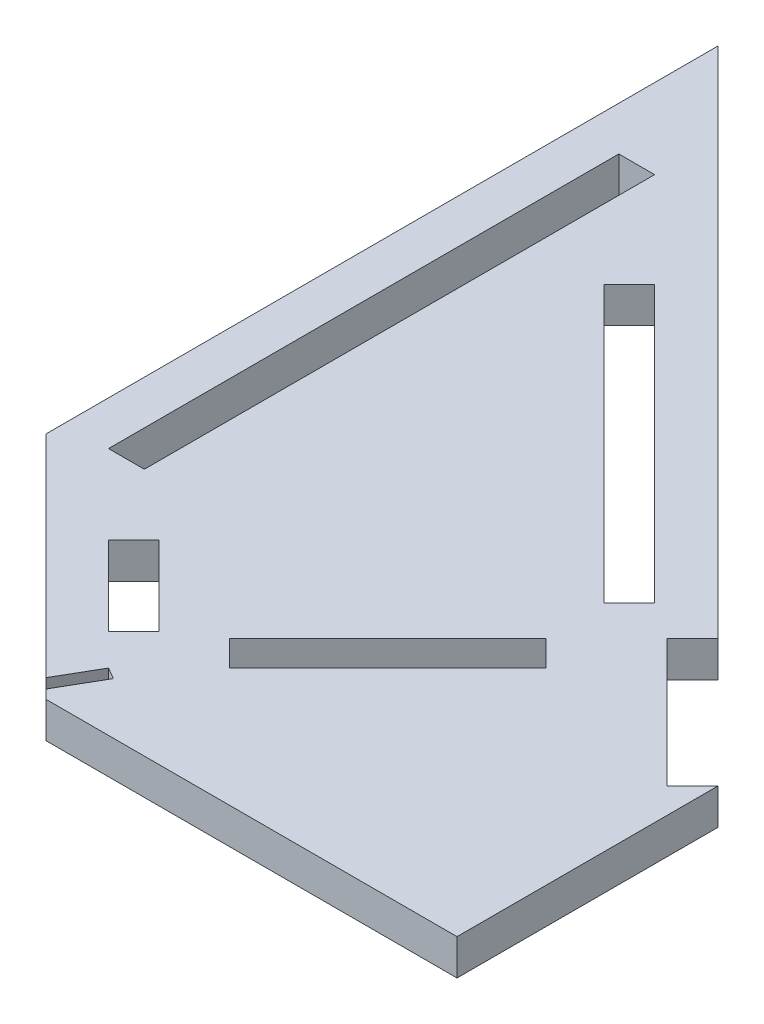
SolidWorks part; units mm, degrees
ref_plane "Front Plane" through (0, 0, 0) normal (0, 0, 1) x (1, 0, 0)
ref_plane "Top Plane" through (0, 0, 0) normal (0, 1, 0) x (1, 0, 0)
ref_plane "Right Plane" through (0, 0, 0) normal (1, 0, 0) x (0, 0, -1)
sketch "Sketch1" plane through (0, 0, 0) normal (0, 1, 0) x (1, 0, 0)
  line L0 (0, 0) -> (0, 58.25)
  line L1 (0, 58.25) -> (-143.0789, 201.3289)
  line L2 (-143.0789, 201.3289) -> (-143.0789, 51.3289)
  line L3 (-143.0789, 51.3289) -> (-95.9462, 4.1962)
  line L4 (-91.75, 0) -> (0, 0)
  line L5 (-93.75, 2) -> (-91.75, 0)
  line L6 (-82.9929, 32.1972) -> (-77.336, 26.5404) construction
  line L7 (-47.6375, 67.5526) -> (-82.9929, 32.1972) construction
  line L8 (-47.6375, 67.5526) -> (-41.9807, 61.8957) construction
  line L17 (-41.9807, 61.8957) -> (-77.336, 26.5404) construction
  line L18 (-109.7154, 142.5174) -> (-48.0839, 80.886)
  line L19 (-48.0839, 80.886) -> (-42.4271, 86.5429)
  line L20 (-42.4271, 86.5429) -> (-104.0585, 148.1743)
  line L21 (-104.0585, 148.1743) -> (-109.7154, 142.5174)
  line L22 (-109.7154, 142.5174) -> (-48.0839, 80.886)
  line L23 (-48.0839, 80.886) -> (-42.4271, 86.5429)
  line L24 (-42.4271, 86.5429) -> (-104.0585, 148.1743)
  line L25 (-104.0585, 148.1743) -> (-109.7154, 142.5174)
  line L34 (-125.2717, 55.4575) -> (-125.2717, 169.3875)
  line L35 (-125.2717, 169.3875) -> (-133.2717, 169.3875)
  line L36 (-133.2717, 169.3875) -> (-133.2717, 55.4575)
  line L37 (-133.2717, 55.4575) -> (-125.2717, 55.4575)
  line L38 (-125.2717, 55.4575) -> (-125.2717, 169.3875)
  line L39 (-125.2717, 169.3875) -> (-133.2717, 169.3875)
  line L40 (-133.2717, 169.3875) -> (-133.2717, 55.4575)
  line L41 (-133.2717, 55.4575) -> (-125.2717, 55.4575)
  line L42 (-82.9929, 32.1972) -> (-77.336, 26.5404)
  line L43 (-47.6375, 67.5526) -> (-82.9929, 32.1972)
  line L44 (-47.6375, 67.5526) -> (-41.9807, 61.8957)
  line L45 (-41.9807, 61.8957) -> (-77.336, 26.5404)
  line L47 (-115.594, 37.7798) -> (-97.9164, 20.1022)
  line L50 (-97.9164, 20.1022) -> (-92.2595, 25.759)
  line L52 (-92.2595, 25.759) -> (-109.9372, 43.4367)
  line L54 (-109.9372, 43.4367) -> (-115.594, 37.7798)
  line L55 (-34.1283, 81.0618) -> (-5.6601, 52.5937)
  line L56 (-5.6601, 52.5937) -> (-0.0033, 58.2506)
  line L57 (-0.0033, 58.2506) -> (-28.4714, 86.7187)
  line L58 (-28.4714, 86.7187) -> (-34.1283, 81.0618)
  line L59 (-34.1283, 81.0618) -> (-5.6601, 52.5937)
  line L60 (-5.6601, 52.5937) -> (-0.0033, 58.2506)
  line L61 (-0.0033, 58.2506) -> (-28.4714, 86.7187)
  line L62 (-28.4714, 86.7187) -> (-34.1283, 81.0618)
  line L63 (-115.594, 37.7798) -> (-97.9164, 20.1022)
  line L64 (-97.9164, 20.1022) -> (-92.2595, 25.759)
  line L65 (-92.2595, 25.759) -> (-109.9372, 43.4367)
  line L66 (-109.9372, 43.4367) -> (-115.594, 37.7798)
  line L139 (-298.2472, -352.1996) -> (-88.2472, 11.5311)
  line L140 (-300.8453, -350.6996) -> (-298.2472, -352.1996)
  line L141 (-90.8453, 13.0311) -> (-300.8453, -350.6996)
  line L142 (-88.2472, 11.5311) -> (-90.8453, 13.0311)
  line L143 (-298.2472, -352.1996) -> (-88.2472, 11.5311)
  line L144 (-300.8453, -350.6996) -> (-298.2472, -352.1996)
  line L145 (-90.8453, 13.0311) -> (-300.8453, -350.6996)
  line L146 (-88.2472, 11.5311) -> (-90.8453, 13.0311)
  point P9 (0, 0)
  dimension "D1" = 135
  dimension "D2" = 150
  dimension "D3" = 72.59
  dimension "D4" = 91.75
  dimension "D5" = 0
  dimension "D6" = 0
  dimension "D7" = 0
  dimension "D8" = 0
  dimension "D9" = 0
extrude "Boss-Extrude1" add sketch "Sketch1" along normal blind 8 contours L62 L1 L2 L3 L5 L4 L0 L59 L41 L40 L39 L38 L25 L24 L23 L22 L44 L45 L42 L43 region at (-80.4323, 0, -73.1393)
